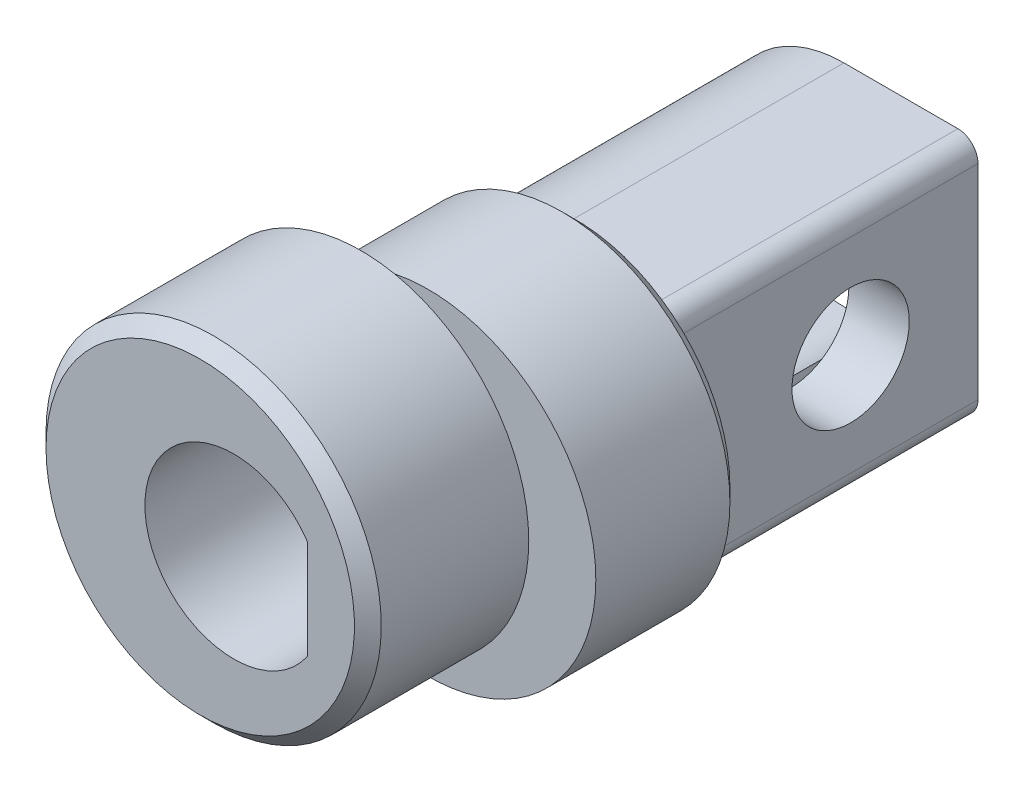
SolidWorks part; units mm, degrees
ref_plane "Ebene vorne" through (0, 0, 0) normal (0, 0, 1) x (1, 0, 0)
ref_plane "Ebene oben" through (0, 0, 0) normal (0, 1, 0) x (1, 0, 0)
ref_plane "Ebene rechts" through (0, 0, 0) normal (1, 0, 0) x (0, 0, -1)
ref_plane "Plane2" through (0, 0, 0.4) normal (0, 0, 1) x (1, 0, 0)
sketch "Sketch10" plane through (0, 0, 0.4) normal (0, 0, 1) x (1, 0, 0)
  circle A0 centre (1, 0) radius 5
extrude "Boss-Extrude4" add sketch "Sketch10" along normal blind 4.2 and the other way blind 0.2
sketch "Sketch11" plane through (0, 0, 0.2) normal (0, 0, -1) x (-1, 0, 0)
  line L0 (-4, -3.05) -> (-4, 3.05)
  line L1 (-3.4, 3.65) -> (0, 3.65)
  line L2 (0, -3.65) -> (-3.4, -3.65)
  arc A0 (-3.4, -3.65) -> (-4, -3.05) centre (-3.4, -3.05) cw
  arc A1 (-4, 3.05) -> (-3.4, 3.65) centre (-3.4, 3.05) cw
  arc A2 (0, 3.65) -> (0, -3.65) centre (0, 0) cw
extrude "Boss-Extrude5" add sketch "Sketch11" along normal blind 9
ref_plane "Plane3" through (0, 0, 4.6) normal (0, 0, -1) x (-1, 0, 0)
sketch "Sketch16" plane through (0, 0, 4.6) normal (0, 0, -1) x (-1, 0, 0)
  circle A0 centre (1, 0) radius 5
extrude "Boss-Extrude6" add sketch "Sketch16" against normal blind 4.8
sketch "Sketch17" plane through (0, 0, 9.4) normal (0, 0, 1) x (1, 0, 0)
  line L0 (2.2, -1.4773) -> (2.2, 1.4773)
  arc A0 (2.2, 1.4773) -> (2.2, -1.4773) centre (0, 0) ccw
extrude "Cut-Extrude2" cut sketch "Sketch17" against normal through all
hole_wizard "HoleWzd2" positions "Sketch19" profile "Sketch18" hole size "Ø3.5" standard "ANSI Metric"
sketch "Sketch19" plane through (4, 0, 0) normal (1, 0, 0) x (0, 0, -1)
  point P0 (5, 0)
sketch "Sketch18" plane through (4, 0, -5) normal (0, 1, 0) x (0, 0, -1)
  line L0 (0, 0) -> (0, 1.8)
  line L1 (0, 1.8) -> (1.75, 1.8)
  line L2 (1.75, 1.8) -> (1.75, 0)
  line L5 (1.75, 0) -> (0, 0)
  line L11 (0, -6.35) -> (0, 107.95) construction
  dimension "Thru Hole Dia." = 3.5
  dimension "Thru Hole Depth" = 1.8
chamfer "Chamfer2" distance 0.4 angle 45 2 edges at (-6, 0, 9.4) (6, 0, 0.2)
